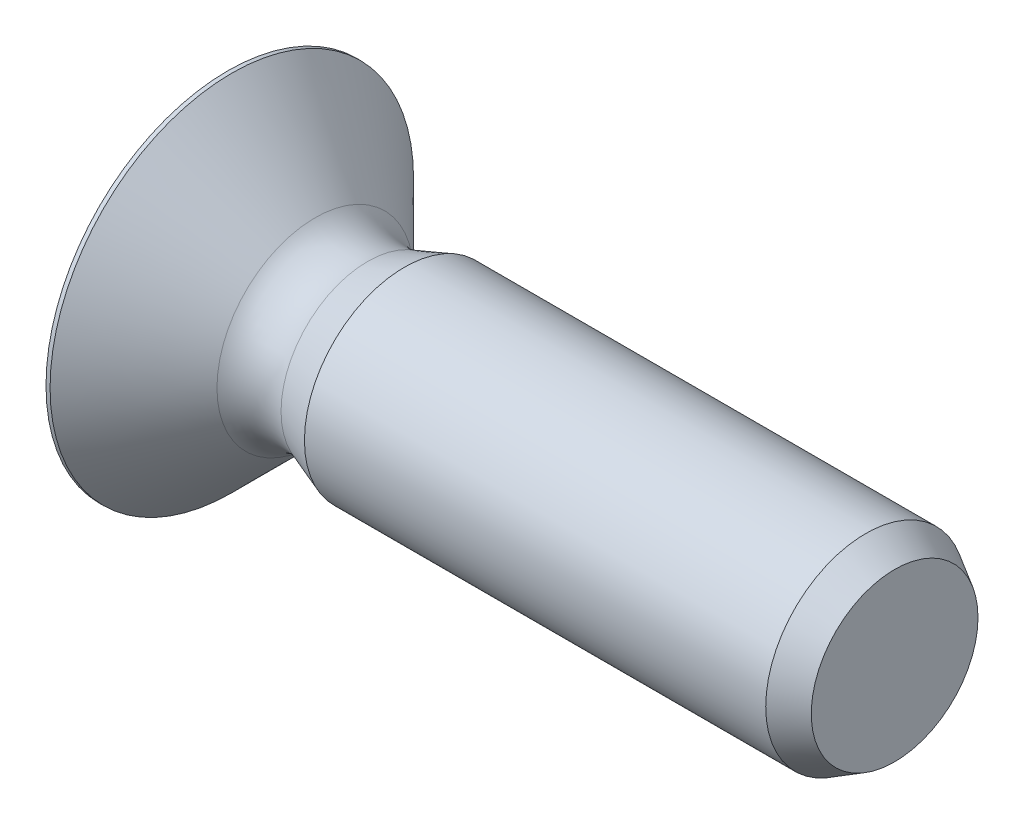
SolidWorks part; units mm, degrees
ref_plane "Front" through (0, 0, 0) normal (0, 0, 1) x (1, 0, 0)
ref_plane "Top" through (0, 0, 0) normal (0, 1, 0) x (1, 0, 0)
ref_plane "Right" through (0, 0, 0) normal (1, 0, 0) x (0, 0, -1)
sketch "Sketch1" plane through (0, 0, 0) normal (0, 0, 1) x (1, 0, 0)
  line L0 (-38.1054, 0) -> (11.3165, 0) construction
  line L1 (20, 0) -> (20, 3)
  line L2 (20, 3) -> (5.3, 3)
  line L3 (5.3, 3) -> (3.3, 2.2721)
  line L4 (3.3, 2.2721) -> (0.1221, 5.45)
  line L5 (20, 0) -> (0, 0)
  line L6 (0.1221, 5.45) -> (0, 5.45)
  line L7 (0, 5.45) -> (0, 0)
  dimension "l" = 20
  dimension "D1" = 45
  dimension "D2" = 20
  dimension "dk" = 10.9
  dimension "k" = 3.3
revolve "Base" add sketch "Sketch1" angle 360 about L0
cosmetic thread "ThreadCosmetic1" [suppressed] parameters "D2"=5
sketch "Sketch2" plane through (0, 0, 0) normal (0, 1, 0) x (1, 0, 0)
  line L0 (21.3282, 0) -> (6.3612, 0) construction
  line L2 (19.134, -3) -> (20, -2.5)
  line L6 (20, -2.5) -> (20, -3)
  line L7 (20, -3) -> (19.134, -3)
  dimension "D1" = 30
  dimension "D2" = 5
  dimension "D3" = 6
revolve "BaseEnd" cut sketch "Sketch2" angle 360 about L0
sketch "Sketch3" plane through (0, 0, 0) normal (1, 0, 0) x (0, 0, -1)
  line L0 (0, 0) -> (-3.9695, 0) construction
  line L1 (0, 0) -> (0, 3.5828) construction
  line L2 (0.73, 3.65) -> (-0.73, 3.65)
  line L3 (-0.73, 3.65) -> (-0.73, 0.73)
  line L4 (-0.73, 0.73) -> (-3.65, 0.73)
  line L5 (-3.65, 0.73) -> (-3.65, -0.73)
  line L6 (-0.73, -0.73) -> (-3.65, -0.73)
  line L7 (-0.73, -3.65) -> (-0.73, -0.73)
  line L8 (0.73, -3.65) -> (-0.73, -3.65)
  line L9 (0.73, -3.65) -> (0.73, -0.73)
  line L10 (0.73, -0.73) -> (3.65, -0.73)
  line L11 (3.65, 0.73) -> (3.65, -0.73)
  line L12 (0.73, 0.73) -> (3.65, 0.73)
  line L13 (0.73, 3.65) -> (0.73, 0.73)
  point P4 (3.65, 0)
  point P10 (-3.65, 0)
  point P14 (0, -3.65)
  point P19 (0, 3.65)
  dimension "D2" = 1.46
extrude "CrossRecess" cut sketch "Sketch3" along normal blind 1.65
draft "Draft1" type of draft neutral plane draft angle 45 faces to draft 4 face at (0.825, -3.65, 0) face at (0.825, 0, -3.65) face at (0.825, 0, 3.65) face at (0.825, 3.65, 0) neutral plane through (0, 5.45, 0) neutral plane normal (-1, 0, 0) parameters "D1"=45
fillet "Fillet1" radius 1.5 1 edges at (3.3, 0, 2.2721)
sketch "Sketch5" plane through (0, 0, 0) normal (0, 0, 1) x (1, 0, 0)
  line L0 (19.1269, 3.0141) -> (19.141, 3.0141)
  line L1 (19.141, 3.0141) -> (19.141, 3)
  line L2 (19.141, 3) -> (19.134, 2.9878)
  line L3 (19.134, 2.9878) -> (19.1269, 3)
  line L4 (19.1269, 3) -> (19.1269, 3.0141)
  line L5 (0, 0) -> (20.5492, 0) construction
  line L6 (0, 5.45) -> (0, -5.45) construction
  line L7 (19.134, 3) -> (19.134, -3) construction
  dimension "D1" = 6
  dimension "D2" = 2.9878
revolve "Cut-Revolve10" [suppressed] cut sketch "Sketch5" angle 360 about L5
pattern_linear "LPattern10" [suppressed] count 862 spacing 0.0171 along (-1, 0, 0) of bodies 105
sketch "Sketch4" plane through (0, 0, 0) normal (0, 0, 1) x (1, 0, 0)
  line L0 (14.0155, 0) -> (-1.5304, 0) construction
  line L1 (2.6243, 2.9478) -> (0.1221, 5.45) construction
  line L2 (3.3125, 2.9878) -> (8.8873, 2.9878)
  line L3 (8.8873, 2.9878) -> (10.1774, 3)
  line L4 (2.5721, 3) -> (3.2875, 2.988)
  line L5 (10.1774, 3) -> (2.5721, 3)
  line L7 (20, -2.5) -> (20, 2.5) construction
  arc A0 (3.3125, 2.9878) -> (3.2875, 2.988) centre (3.3125, 4.4878) cw
  point P14 (3.3, 2.9878)
  dimension "D3" = 1.5
  dimension "D1" = 2.9878
  dimension "b" = 9.8226
  dimension "D2" = 16.7
  dimension "D4" = 6
revolve "Cut-Revolve2" [suppressed] cut sketch "Sketch4" angle 360 about L0
equation "\"D2@ThreadCosmetic1\" = \"d@Sketch1\" - 1"
equation "\"D2@Sketch2\" = \"D2@ThreadCosmetic1\""
equation "\"D3@Sketch2\" = \"d@Sketch1\""
equation "\"D2@Sketch3\" = \"m@Sketch3\" / 5"
equation "\"D1@Sketch4\" = \"d@Sketch1\" / 2 - \"a@Sketch1\" * tan ( 3.14 / 9 ) "
equation "\"D1@CrossRecess\" = \"k@Sketch1\" /2"
equation "\"D2@Sketch4\" = \"l@Sketch1\" - \"k@Sketch1\""
equation "\"D3@Sketch4\" = \"r@Fillet1\""
equation "\"D4@Sketch4\" = \"d@Sketch1\""
equation "\"D1@Sketch5\" = \"d@Sketch1\""
equation "\"D2@Sketch5\" = \"d@Sketch1\" / 2 - \"a@Sketch1\" * tan ( 3.14 / 9 ) "
equation "\"D3@LPattern10\" = (  \"D1@Sketch5\" / 2 - \"D2@Sketch5\" )  * 1.4"
equation "\"D1@LPattern10\" = (  \"l@Sketch1\" - \"k@Sketch1\" - \"a@Sketch1\" )  / \"D3@LPattern10\""
